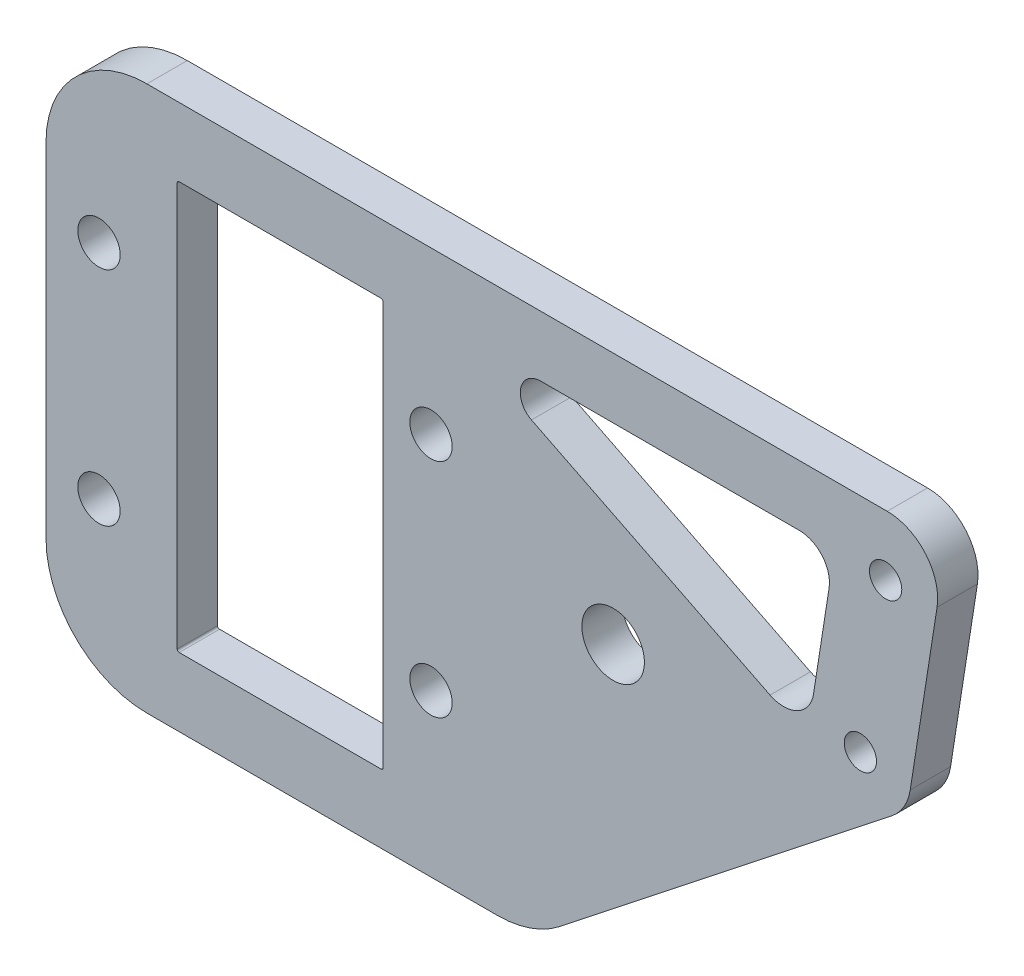
SolidWorks part; units mm, degrees
material "玻纤"
ref_plane "前视基准面" through (0, 0, 0) normal (0, 0, 1) x (1, 0, 0)
ref_plane "上视基准面" through (0, 0, 0) normal (0, 1, 0) x (1, 0, 0)
ref_plane "右视基准面" through (0, 0, 0) normal (1, 0, 0) x (0, 0, -1)
sketch "草图1" plane through (0, 0, 0) normal (0, 0, 1) x (1, 0, 0)
  line L0 (-10.2, 20.2) -> (10.2, 20.2)
  line L1 (-10, -20) -> (10, -20) construction
  line L2 (-10, -20) -> (-10, 20) construction
  line L3 (-10, 20) -> (10, 20) construction
  line L4 (10, -20) -> (10, 20) construction
  line L5 (-10, -20) -> (10, 20) construction
  line L6 (-10, 20) -> (10, -20) construction
  line L7 (10.2, -20.2) -> (10.2, 20.2)
  line L8 (-10.2, -20.2) -> (10.2, -20.2)
  line L9 (-10.2, -20.2) -> (-10.2, 20.2)
  line L10 (-13.2, 27) -> (60.1562, 27)
  line L11 (33, 25) -> (33, -25) construction
  line L12 (21.5311, -27) -> (-13.2, -27)
  line L13 (-23.2, -17) -> (-23.2, 17)
  line L15 (27.7237, -24.8519) -> (60.5963, 1.0741)
  line L16 (62.4401, 4.2281) -> (65.0963, 21.2281)
  circle A0 centre (33, 2) radius 3.1
  arc A1 (-13.2, -27) -> (-23.2, -17) centre (-13.2, -17) cw
  arc A2 (-13.2, 27) -> (-23.2, 17) centre (-13.2, 17) ccw
  circle A6 centre (33, 2) radius 12.5 construction
  circle A9 centre (60, 21) radius 1.6
  circle A10 centre (57.5, 5) radius 1.6
  arc A12 (60.5963, 1.0741) -> (62.4401, 4.2281) centre (57.5, 5) ccw
  arc A13 (21.5311, -27) -> (27.7237, -24.8519) centre (21.5311, -17) ccw
  arc A14 (65.0963, 21.2281) -> (60.1562, 27) centre (60.1562, 22) ccw
  point P0 (0, 0)
  point P32 (25, -27)
  dimension "D8" = 6.2
  dimension "D10" = 10
  dimension "D11" = 3.2
  dimension "D12" = 19
  dimension "D13" = 25
  dimension "D9" = 25
  dimension "D14" = 27
  dimension "D15" = 3.2
  dimension "D18" = 10
  dimension "D20" = 10
  dimension "D21" = 5
  dimension "D1" = 40
  dimension "D2" = 20
  dimension "D3" = 0.2
  dimension "D4" = 7
  dimension "D5" = 7
  dimension "D6" = 13
  dimension "D7" = 43
  dimension "D16" = 3
  dimension "D17" = 24.5
  dimension "D19" = 25
  dimension "D22" = 5
extrude "凸台-拉伸1" add sketch "草图1" along normal blind 4
fillet "圆角1" radius 0.2 4 edges at (10.2, -20.2, 2) (-10.2, -20.2, 2) (-10.2, 20.2, 2) (10.2, 20.2, 2)
sketch "草图2" plane through (0, 0, 4) normal (0, 0, 1) x (1, 0, 0)
  line L0 (14.95, 11) -> (14.95, -11) construction
  line L1 (9.95, 20.25) -> (9.95, -49979.75) construction
  line L2 (0, 0) -> (50000, 0) construction
  line L3 (10.2, -20) -> (10.2, 20) construction
  line L4 (0, 0.6321) -> (0, 50000.6321) construction
  line L5 (-17.95, 11) -> (-17.95, -11) construction
  circle A0 centre (14.95, 11) radius 2.1
  circle A4 centre (14.95, -11) radius 2.1
  circle A5 centre (-17.95, -11) radius 2.1
  circle A6 centre (-17.95, 11) radius 2.1
  dimension "D1" = 4.2
  dimension "D2" = 22
  dimension "D3" = 17.95
  dimension "D6" = 4.2
  dimension "D7" = 4.2
  dimension "D8" = 17.95
  dimension "D4" = 0.25
  dimension "D5" = 5
extrude "切除-拉伸1" cut sketch "草图2" against normal blind 4
sketch "草图3" plane through (0, 0, 4) normal (0, 0, 1) x (1, 0, 0)
  line L0 (25.798, 21) -> (51.4342, 21)
  line L1 (54.3982, 17.5369) -> (52.8522, 7.6426)
  line L2 (48.5495, 5.4209) -> (24.9056, 17.2102)
  line L3 (60.1562, 27) -> (-13.2, 27) construction
  line L4 (14.95, 11) -> (33, 2) construction
  line L5 (57.5, 5) -> (60, 21) construction
  line L6 (62.4401, 4.2281) -> (65.0963, 21.2281) construction
  arc A0 (54.3982, 17.5369) -> (51.4342, 21) centre (51.4342, 18) ccw
  arc A1 (24.9056, 17.2102) -> (25.798, 21) centre (25.798, 19) cw
  arc A2 (48.5495, 5.4209) -> (52.8522, 7.6426) centre (49.8882, 8.1057) ccw
  dimension "3" = 3
  dimension "D2" = 2
  dimension "D3" = 3
  dimension "D1" = 6
  dimension "D4" = 10
  dimension "D5" = 10
extrude "切除-拉伸2" cut sketch "草图3" against normal blind 10
equation "\"4。2\"=3.2"
equation "\"6。2\"=6.5866"
equation "\"3。2\"=6.2"
equation "\"12。5\"=10"
